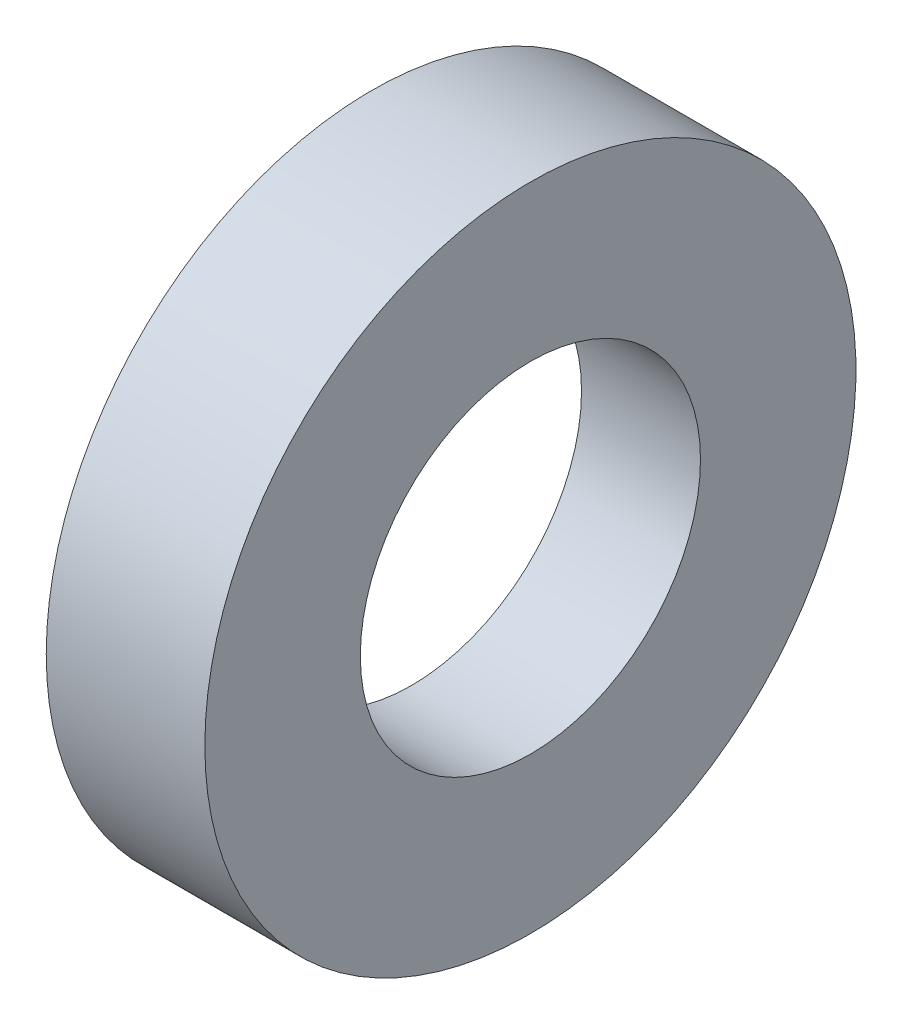
SolidWorks part; units mm, degrees
ref_plane "Front Plane" through (0, 0, 0) normal (0, 0, 1) x (1, 0, 0)
ref_plane "Top Plane" through (0, 0, 0) normal (0, 1, 0) x (1, 0, 0)
ref_plane "Right Plane" through (0, 0, 0) normal (1, 0, 0) x (0, 0, -1)
sketch "Sketch1" plane through (0, 0, 0) normal (0, 0, 1) x (1, 0, 0)
  line L0 (4.5816, 1.63) -> (5.7216, 1.63)
  line L1 (5.7216, 1.63) -> (5.7216, 3.12)
  line L2 (5.7216, 3.12) -> (4.2016, 3.12)
  line L3 (4.2016, 3.12) -> (4.2016, 2.23)
  line L4 (4.2016, 2.23) -> (4.5816, 2.23)
  line L5 (4.5816, 2.23) -> (4.5816, 1.63)
  line L6 (0, 0) -> (7.2765, 0) construction
  dimension "D1" = 1.63
  dimension "D2" = 1.49
  dimension "D3" = 0.89
  dimension "D4" = 1.14
  dimension "D5" = 1.52
revolve "Revolve1" add sketch "Sketch1" angle 360 about L6
